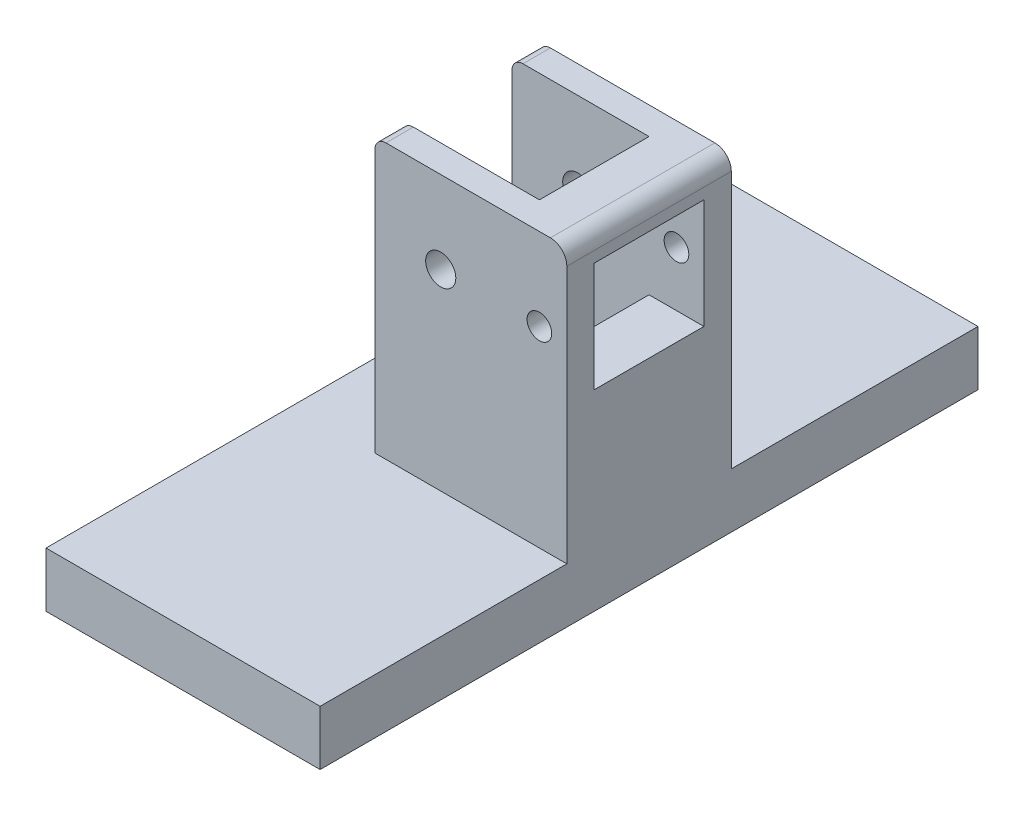
SolidWorks part; units mm, degrees
ref_plane "Front Plane" through (0, 0, 0) normal (0, 0, 1) x (1, 0, 0)
ref_plane "Top Plane" through (0, 0, 0) normal (0, 1, 0) x (1, 0, 0)
ref_plane "Right Plane" through (0, 0, 0) normal (1, 0, 0) x (0, 0, -1)
sketch "Sketch4" plane through (0, 0, 0) normal (0, 1, 0) x (1, 0, 0)
  line L1 (0, 0) -> (40, 0)
  line L2 (0, 0) -> (0, 80)
  line L3 (0, 80) -> (40, 80)
  line L4 (40, 0) -> (40, 80)
  dimension "D1" = 80
  dimension "D2" = 40
extrude "Boss-Extrude4" add sketch "Sketch4" along normal blind 5
sketch "Sketch5" plane through (0, 5, 0) normal (0, 1, 0) x (1, 0, 0)
  line L0 (40, 40) -> (30, 40)
  line L1 (30, 30) -> (30, 50) construction
  line L2 (40, 50) -> (30, 50)
  line L3 (30, 50) -> (30, 55)
  line L4 (0, 80) -> (0, 0)
  line L5 (0, 0) -> (40, 0)
  line L6 (40, 0) -> (40, 80)
  line L7 (40, 80) -> (0, 80)
  line L8 (0, 80) -> (0, 0)
  line L9 (0, 0) -> (40, 0)
  line L10 (40, 0) -> (40, 80)
  line L11 (40, 80) -> (0, 80)
  line L12 (30, 55) -> (40, 55)
  line L13 (40, 55) -> (40, 50)
  line L14 (40, 30) -> (30, 30)
  line L15 (30, 30) -> (30, 25)
  line L16 (30, 25) -> (40, 25)
  line L17 (40, 25) -> (40, 30)
  point P9 (30, 40)
  line M11 (40, 0) -> (40, 80)
  dimension "D2" = 10
  dimension "D3" = 10
  dimension "D4" = 5
  dimension "D5" = 5
  dimension "D1" = 0
extrude "Boss-Extrude6" add sketch "Sketch5" along normal blind 50 contours L12 L3 L2 M11 | L15 L16 L10 L14 region at (35, 5, -52.5) region at (35, 5, -27.5)
sketch "Sketch7" plane through (0, 0, -50) normal (0, 0, 1) x (1, 0, 0)
  line L1 (30, 5) -> (40, 5)
  line L2 (30, 5) -> (30, 30)
  line L3 (30, 30) -> (40, 30)
  line L4 (40, 5) -> (40, 30)
  line L5 (40, 55) -> (40, 5) construction
  line L7 (30, 55) -> (40, 55)
  line L8 (30, 55) -> (30, 50)
  line L9 (30, 50) -> (40, 50)
  line L10 (40, 55) -> (40, 50)
  dimension "D1" = 25
  dimension "D2" = 10
  dimension "D3" = 5
extrude "Boss-Extrude7" add sketch "Sketch7" along normal up to surface (20 mm away) contours L8 L7 L10 L9 | L2 L1 L4 L3 up to face at (35, 30, -30)
sketch "Sketch9" plane through (0, 0, 0) normal (-1, 0, 0) x (0, 0, 1)
  line L4 (-80, 0) -> (0, 0)
  line L5 (0, 0) -> (0, 5)
  line L6 (0, 5) -> (-80, 5)
  line L7 (-80, 5) -> (-80, 0)
  line L8 (-80, 0) -> (0, 0)
  line L9 (0, 0) -> (0, 5)
  line L10 (0, 5) -> (-80, 5)
  line L12 (-80, 5) -> (-80, 0)
  dimension "D1" = 0
extrude "Boss-Extrude9" add sketch "Sketch9" along normal blind 10
sketch "Sketch10" plane through (0, 0, 0) normal (0, 0, 1) x (1, 0, 0)
  line L4 (-10, 0) -> (40, 0)
  line L5 (40, 0) -> (40, 5)
  line L6 (40, 5) -> (-10, 5)
  line L7 (-10, 5) -> (-10, 0)
  line L8 (-10, 0) -> (40, 0)
  line L9 (40, 0) -> (40, 5)
  line L10 (40, 5) -> (-10, 5)
  line L11 (-10, 5) -> (-10, 0)
  dimension "D1" = 0
extrude "Boss-Extrude10" add sketch "Sketch10" along normal blind 20
sketch "Sketch11" plane through (0, 0, -50) normal (0, 0, 1) x (1, 0, 0)
  line L0 (30, 40) -> (35, 40)
  line L4 (30, 30) -> (40, 30)
  line L5 (40, 30) -> (40, 50)
  line L6 (40, 50) -> (30, 50)
  line L7 (30, 50) -> (30, 30)
  line L8 (30, 30) -> (40, 30)
  line L9 (40, 30) -> (40, 50)
  line L10 (40, 50) -> (30, 50)
  line L11 (30, 50) -> (30, 30)
  circle A0 centre (35, 40) radius 2.25
  dimension "D3" = 4.5
  dimension "D2" = 5
  dimension "D1" = 0
extrude "Cut-Extrude1" cut sketch "Sketch11" against normal mid plane 50 contours A0 region at (35, 42.1864, -50)
sketch "Sketch12" plane through (0, 0, -25) normal (0, 0, 1) x (1, 0, 0)
  circle A0 centre (35, 40) radius 2.25 construction
  circle A1 centre (35, 40) radius 2.25
  circle A2 centre (35, 40) radius 4
  dimension "D1" = 8
extrude "Cut-Extrude2" cut sketch "Sketch12" against normal blind 2
sketch "Sketch13" plane through (0, 0, -55) normal (0, 0, -1) x (-1, 0, 0)
  circle A0 centre (-35, 40) radius 2.25 construction
  circle A1 centre (-35, 40) radius 2.25
  circle A2 centre (-35, 40) radius 4
  dimension "D1" = 8
sketch "Sketch15" plane through (30, 0, 0) normal (-1, 0, 0) x (0, 0, 1)
  line L1 (-55, 55) -> (-50, 55)
  line L2 (-55, 55) -> (-55, 5)
  line L3 (-55, 5) -> (-50, 5)
  line L4 (-50, 55) -> (-50, 5)
  line L5 (-25, 55) -> (-30, 55)
  line L6 (-25, 55) -> (-25, 5)
  line L7 (-25, 5) -> (-30, 5)
  line L8 (-30, 55) -> (-30, 5)
  dimension "D1" = 50
  dimension "D2" = 5
  dimension "D3" = 50
  dimension "D4" = 5
extrude "Boss-Extrude11" add sketch "Sketch15" along normal blind 20
sketch "Sketch16" plane through (0, 0, -25) normal (0, 0, 1) x (1, 0, 0)
  line L0 (35, 40) -> (17, 40)
  circle A0 centre (35, 40) radius 4 construction
  circle A1 centre (35, 40) radius 4
  circle A2 centre (17, 40) radius 2.75
  dimension "D2" = 5.5
  dimension "D1" = 18
extrude "Cut-Extrude4" cut sketch "Sketch16" against normal up to surface (30 mm away) contours A2 region at (14.3278, 40, -25) up to face at (32.75, 40, -55)
sketch "Sketch17" plane through (0, 0, -25) normal (0, 0, 1) x (1, 0, 0)
  circle A0 centre (17, 40) radius 2.75 construction
  circle A1 centre (17, 40) radius 2.75
  circle A2 centre (17, 40) radius 4.5
  dimension "D1" = 9
sketch "Sketch18" plane through (0, 0, -55) normal (0, 0, -1) x (-1, 0, 0)
  circle A0 centre (-17, 40) radius 2.75 construction
  circle A1 centre (-17, 40) radius 2.75
  circle A2 centre (-17, 40) radius 4.5
  dimension "D1" = 9
fillet "Fillet3" radius 3 1 edges at (40, 55, -40)
sketch "Sketch19" plane through (10, 0, 0) normal (-1, 0, 0) x (0, 0, 1)
  line L4 (-55, 55) -> (-55, 5)
  line L5 (-55, 5) -> (-50, 5)
  line L6 (-50, 5) -> (-50, 55)
  line L7 (-50, 55) -> (-55, 55)
  line L8 (-55, 55) -> (-55, 5)
  line L10 (-50, 5) -> (-50, 55)
  line L11 (-50, 55) -> (-55, 55)
  line L12 (-25, 5) -> (-25, 55)
  line L13 (-25, 55) -> (-30, 55)
  line L14 (-30, 55) -> (-30, 5)
  line L15 (-30, 5) -> (-25, 5)
  line L16 (-25, 5) -> (-25, 55)
  line L17 (-25, 55) -> (-30, 55)
  line L18 (-30, 55) -> (-30, 5)
  line L20 (-55, 5) -> (-50, 5)
  line L21 (-30, 5) -> (-25, 5)
  dimension "D1" = 0
  dimension "D2" = 0
extrude "Boss-Extrude12" add sketch "Sketch19" along normal blind 5
sketch "Sketch20" plane through (0, 0, -27) normal (0, 0, 1) x (1, 0, 0)
  circle A0 centre (35, 40) radius 2.25 construction
  circle A1 centre (35, 40) radius 4
  circle A2 centre (35, 40) radius 4
  circle A3 centre (35, 40) radius 2.25
  dimension "D1" = 0
extrude "Boss-Extrude13" add sketch "Sketch20" along normal up to surface (2 mm away) up to face at (19.75, 40, -25)
sketch "Sketch21" plane through (0, 0, 0) normal (0, -1, 0) x (1, 0, 0)
  line L4 (40, -80) -> (40, 20)
  line L5 (40, 20) -> (-10, 20)
  line L6 (-10, 20) -> (-10, -80)
  line L7 (-10, -80) -> (40, -80)
  line L8 (40, -80) -> (40, 20)
  line L9 (40, 20) -> (-10, 20)
  line L10 (-10, 20) -> (-10, -80)
  line L11 (-10, -80) -> (40, -80)
  dimension "D1" = 0
extrude "Boss-Extrude14" add sketch "Sketch21" along normal blind 5
fillet "Fillet4" radius 2 2 edges at (5, 55, -27.5) (5, 55, -52.5)
sketch "Sketch22" plane through (0, 0, -80) normal (0, 0, -1) x (-1, 0, 0)
  line L4 (-40, 5) -> (-40, -5)
  line L5 (-40, -5) -> (10, -5)
  line L6 (10, -5) -> (10, 5)
  line L7 (10, 5) -> (-40, 5)
  line L8 (-40, 5) -> (-40, -5)
  line L9 (-40, -5) -> (10, -5)
  line L10 (10, -5) -> (10, 5)
  line L11 (10, 5) -> (-40, 5)
  dimension "D1" = 0
extrude "Boss-Extrude15" add sketch "Sketch22" along normal blind 20
